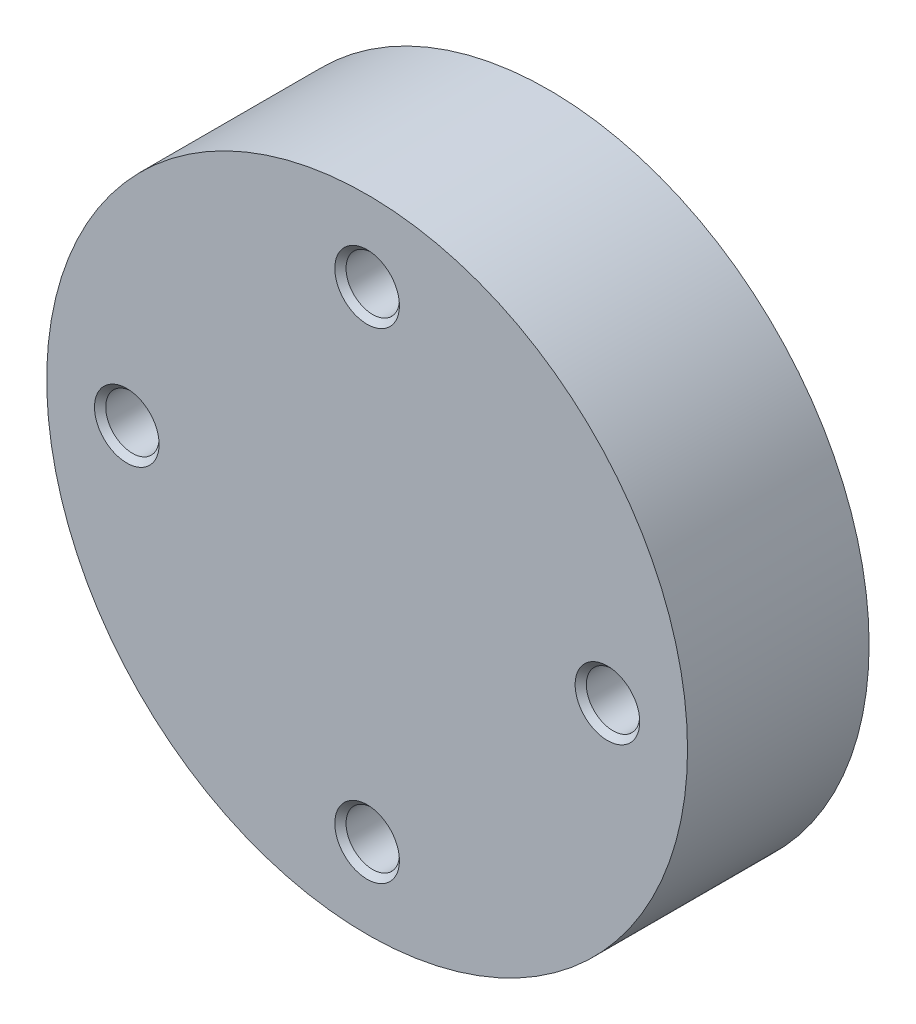
SolidWorks part; units mm, degrees
material "1060 Alloy"
ref_plane "Front Plane" through (0, 0, 0) normal (0, 0, 1) x (1, 0, 0)
ref_plane "Top Plane" through (0, 0, 0) normal (0, 1, 0) x (1, 0, 0)
ref_plane "Right Plane" through (0, 0, 0) normal (1, 0, 0) x (0, 0, -1)
sketch "Sketch1" plane through (0, 0, 0) normal (0, 0, 1) x (1, 0, 0)
  circle A0 centre (0, 0) radius 30
  circle A1 centre (0, 0) radius 15
  dimension "D1" = 60
  dimension "D2" = 30
extrude "Boss-Extrude1" add sketch "Sketch1" along normal blind 17 contours A1 | A0 A1 region at (-29.1515, 0, 0) region at (0, 0, 0)
extrude "Cut-Extrude1" cut sketch "Sketch1<3>" along normal blind 15 contours A1 region at (0, 0, 0)
sketch "Sketch1<3>" plane through (0, 0, 0) normal (0, 0, 1) x (1, 0, 0) same geometry as "Sketch1"
sketch "Sketch2" plane through (0, 0, 17) normal (0, 0, 1) x (1, 0, 0)
  circle A0 centre (0, 0) radius 22.5 construction
  point P3 (0, 22.5)
  point P4 (22.5, 0)
  point P5 (-22.5, 0)
  point P6 (0, -22.5)
  dimension "D1" = 45
hole_wizard "M6 Tapped Hole1" positions "Sketch3" profile "Sketch4" tap size "M6" standard "ISO"
sketch "Sketch3" plane through (0, 0, 17) normal (0, 0, 1) x (1, 0, 0)
  point P0 (0, -22.5)
  point P3 (22.5, 0)
  point P6 (0, 22.5)
  point P9 (-22.5, 0)
sketch "Sketch4" plane through (0, -22.5, 17) normal (1, 0, 0) x (0, -1, 0)
  line L0 (0, 0) -> (0, 10.5022)
  line L1 (0, 10.5022) -> (2.5, 9)
  line L2 (2.5, 9) -> (2.5, 0.525)
  line L3 (2.5, 0.525) -> (3.025, 0)
  line L5 (3.025, 0) -> (0, 0)
  line L6 (-2.5, 0.525) -> (-3.025, 0) construction
  line L10 (0, 10.5022) -> (-2.5, 9) construction
  line L11 (0, -6.35) -> (0, 107.95) construction
  dimension "Tap Drill Dia." = 5
  dimension "Tap Drill Depth" = 9
  dimension "Near C'Sink Dia." = 6.05
  dimension "Near C'Sink Angle" = 90
  dimension "Drill Angle" = 118
cosmetic thread "Hole Thread1" parameters "D1"=6, "D2"=6
cosmetic thread "Hole Thread2" parameters "D1"=6, "D2"=6
cosmetic thread "Hole Thread3" parameters "D1"=6, "D2"=6
cosmetic thread "Hole Thread4" parameters "D1"=6, "D2"=6
